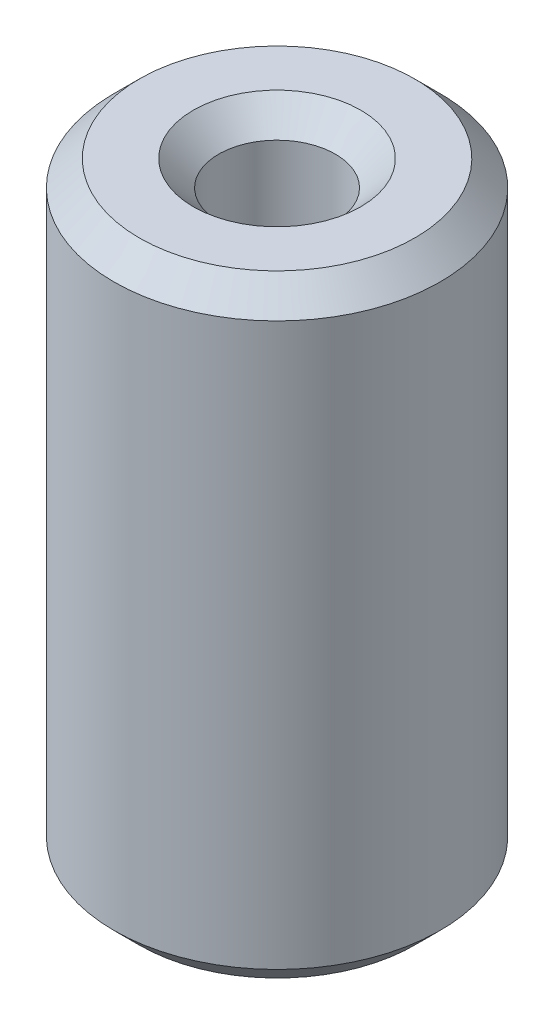
SolidWorks part; units mm, degrees
ref_plane "Front Plane" through (0, 0, 0) normal (0, 0, 1) x (1, 0, 0)
ref_plane "Top Plane" through (0, 0, 0) normal (0, 1, 0) x (1, 0, 0)
ref_plane "Right Plane" through (0, 0, 0) normal (1, 0, 0) x (0, 0, -1)
sketch "Sketch1" plane through (0, 0, 0) normal (0, 1, 0) x (1, 0, 0)
  circle A0 centre (0, 0) radius 15
  dimension "SLEEVE_OD" = 30
extrude "Boss-Extrude1" add sketch "Sketch1" along normal blind 56.3137
sketch "Sketch2" plane through (0, 0, 0) normal (0, 1, 0) x (1, 0, 0)
  circle A0 centre (0, 0) radius 5.3641
  dimension "BORE_D" = 10.7282
extrude "Cut-Extrude1" cut sketch "Sketch2" along normal through all
chamfer "Chamfer1" distance 2.3346 angle 45 4 edges at (0, 56.3137, 5.3641) (0, 0, 5.3641) (0, 0, 15) (0, 56.3137, 15)
